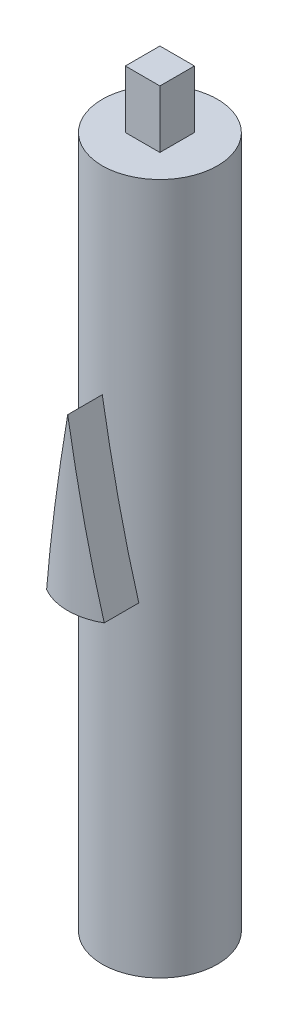
SolidWorks part; units mm, degrees
ref_plane "Front Plane" through (0, 0, 0) normal (0, 0, 1) x (1, 0, 0)
ref_plane "Top Plane" through (0, 0, 0) normal (0, 1, 0) x (1, 0, 0)
ref_plane "Right Plane" through (0, 0, 0) normal (1, 0, 0) x (0, 0, -1)
sketch "Sketch1" plane through (0, 0, 0) normal (0, 1, 0) x (1, 0, 0)
  circle A0 centre (0, 0) radius 5
extrude "Boss-Extrude1" add sketch "Sketch1" along normal blind 60
sketch "Sketch2" plane through (0, 0, 0) normal (0, -1, 0) x (1, 0, 0)
  line L1 (-2.5, 1.5) -> (2.5, 1.5)
  line L2 (-2.5, 1.5) -> (-2.5, -1.5)
  line L3 (-2.5, -1.5) -> (2.5, -1.5)
  line L4 (2.5, 1.5) -> (2.5, -1.5)
  dimension "D1" = 5
  dimension "D2" = 3
  dimension "D3" = 2.5
  dimension "D4" = 1.5
extrude "Cut-Extrude1" cut sketch "Sketch2" against normal blind 6
sketch "Sketch3" plane through (0, 0, 0) normal (0, 0, 1) x (1, 0, 0)
  line L0 (0, 42.7982) -> (-2.5, 28.0659)
  line L1 (-2.5, 28.0659) -> (2.5, 28.0659)
  line L2 (2.5, 28.0659) -> (0, 42.7982)
  dimension "D1" = 5
  dimension "D2" = 2.5
  dimension "D3" = 2.5
extrude "Boss-Extrude2" add sketch "Sketch3" along normal blind 3 from surface starting at face at (0, 60, 5)
ref_point "Point1"
ref_axis "Axis1" through (0, 60, 0) along (0, -1, 0)
sketch "Sketch4" plane through (0, 60, 0) normal (0, 1, 0) x (1, 0, 0)
  line L1 (-1.5, 1.5) -> (1.5, 1.5)
  line L2 (-1.5, 1.5) -> (-1.5, -1.5)
  line L3 (-1.5, -1.5) -> (1.5, -1.5)
  line L4 (1.5, 1.5) -> (1.5, -1.5)
  dimension "D1" = 3
  dimension "D2" = 3
  dimension "D3" = 1.5
  dimension "D4" = 1.5
extrude "Boss-Extrude3" add sketch "Sketch4" along normal blind 5
